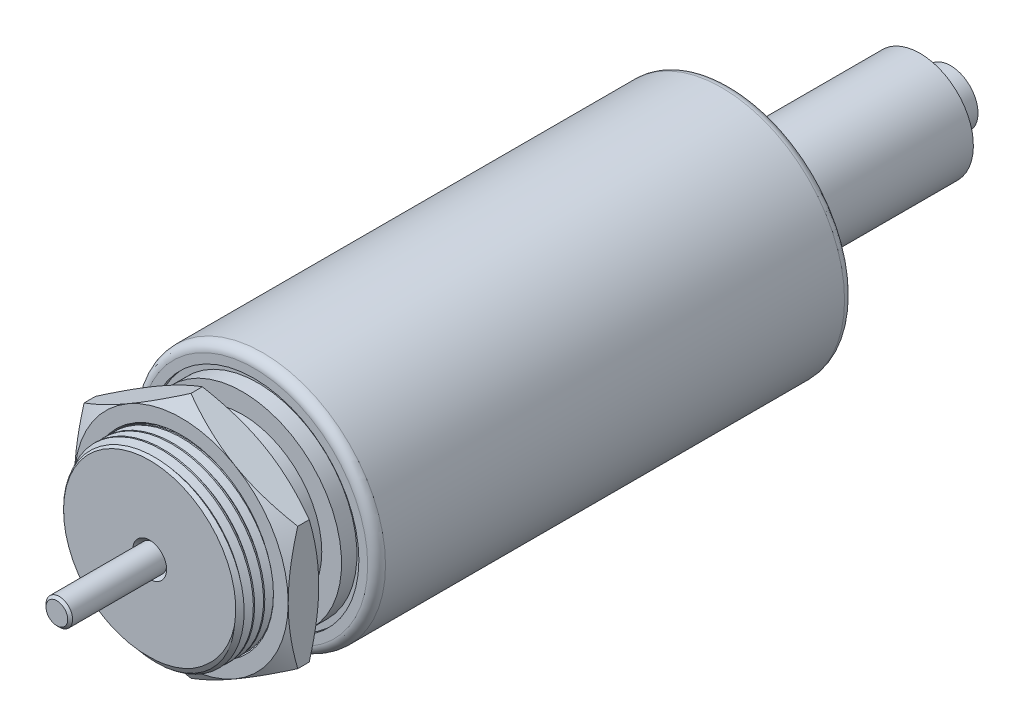
SolidWorks part; units mm, degrees
ref_plane "Front Plane" through (0, 0, 0) normal (0, 0, 1) x (1, 0, 0)
ref_plane "Top Plane" through (0, 0, 0) normal (0, 1, 0) x (1, 0, 0)
ref_plane "Right Plane" through (0, 0, 0) normal (1, 0, 0) x (0, 0, -1)
sketch "Sketch0" plane through (0, 0, 0) normal (1, 0, 0) x (0, 0, -1)
  line L0 (0, 0) -> (50.8, 0) construction
  line L1 (0, 0) -> (-19.304, 0) construction
  line L2 (50.8, 12.7635) -> (50.8, -12.7635) construction
  line L3 (0, 9.464) -> (0, -9.464) construction
  line L4 (-19.304, 1.3843) -> (-19.304, -1.3843) construction
  line L5 (-19.304, 0) -> (-32.004, 0) construction
  line L6 (50.8, 0) -> (63.5, 0) construction
  line L7 (63.5, 0) -> (73.66, 0) construction
  line L8 (70.485, 5.5499) -> (70.485, -5.5499) construction
  line L9 (73.66, 2.8575) -> (73.66, -2.8575) construction
  point P12 (-9.652, 0)
  point P17 (70.485, 0)
  dimension "D1" = 5.715
  dimension "Lg." = 50.8
  dimension "Dia." = 25.527
  dimension "Rod Dia." = 2.7686
  dimension "A" = 32.004
  dimension "Thread OD" = 18.9281
  dimension "Stroke" = 12.7
  dimension "D2" = 3.175
  dimension "D3" = 9.652
  dimension "D4" = 19.304
  dimension "End Dia." = 11.0998
  dimension "D5" = 10.16
sketch "Sketch1" plane through (0, 0, 0) normal (1, 0, 0) x (0, 0, -1)
  line L0 (50.8, 0) -> (0, 0) construction
  line L1 (49.8729, 12.7635) -> (2.1209, 12.7635)
  line L4 (1.6002, 10.922) -> (1.6002, 10.3124)
  line L5 (50.8, 5.5499) -> (50.8, 11.8364)
  line L6 (1.1938, 11.8364) -> (1.1938, 10.922)
  line L7 (1.1938, 10.922) -> (1.6002, 10.922)
  line L8 (1.6002, 10.3124) -> (0, 10.3124)
  line L9 (0, 10.3124) -> (0, 5.5499)
  line L10 (50.8, 5.5499) -> (0, 5.5499)
  line L11 (0, 9.464) -> (0, -9.464) construction
  arc A1 (50.8, 11.8364) -> (49.8729, 12.7635) centre (49.8729, 11.8364) ccw
  arc A2 (1.1938, 11.8364) -> (2.1209, 12.7635) centre (2.1209, 11.8364) cw
  dimension "D1" = 0.9271
  dimension "D4" = 1.1938
  dimension "D5" = 21.844
  dimension "D6" = 0.4064
  dimension "D7" = 20.6248
revolve "Revolve1" add sketch "Sketch1" angle 360 mid plane about L0
sketch "Sketch2" plane through (0, 0, 0) normal (1, 0, 0) x (0, 0, -1)
  line L0 (0, 0) -> (-19.304, 0) construction
  line L3 (-9.652, 1.7653) -> (-9.652, 8.956)
  line L4 (-9.652, 8.956) -> (-9.144, 9.464)
  line L5 (-9.144, 9.464) -> (-2.479, 9.464)
  line L6 (-2.479, 9.464) -> (-1.27, 8.255)
  line L7 (-1.27, 8.255) -> (0, 8.255)
  line L8 (0, 8.255) -> (0, 1.3843)
  line L9 (-9.271, 1.3843) -> (0, 1.3843)
  line L11 (-9.271, 1.3843) -> (-9.652, 1.7653)
  dimension "D1" = 1.27
  dimension "D4" = 0.508
  dimension "D5" = 9.652
  dimension "D2" = 45
  dimension "D6" = 1.209
  dimension "D3" = 45
  dimension "D8" = 0.381
  dimension "D7" = 45
revolve "Revolve2" add sketch "Sketch2" angle 360 mid plane about L0
sketch "Sketch3" plane through (0, 0, 0) normal (1, 0, 0) x (0, 0, -1)
  line L0 (-19.304, 0) -> (0, 0) construction
  line L1 (-19.05, 1.3843) -> (-19.304, 1.1303)
  line L2 (73.66, 0) -> (-19.304, 0)
  line L3 (0, 9.464) -> (0, -9.464) construction
  line L4 (12.7, 1.3843) -> (-19.05, 1.3843)
  line L5 (-19.304, 0) -> (-19.304, 1.1303)
  line L6 (-19.05, 1.3843) -> (-19.304, 1.3843) construction
  line L7 (-19.304, 1.3843) -> (-19.304, 1.1303) construction
  line L8 (0, 0) -> (0, 5.5499) construction
  line L9 (0, 5.5499) -> (12.7, 5.5499) construction
  line L10 (12.7, 5.5499) -> (70.485, 5.5499)
  line L11 (70.485, 5.5499) -> (70.485, 2.8575)
  line L12 (70.485, 2.8575) -> (73.66, 2.8575)
  line L14 (73.66, 2.8575) -> (73.66, 0)
  line L15 (-19.304, 0) -> (-32.004, 0) construction
  line L16 (12.7, 5.5499) -> (12.7, 1.3843)
  line L17 (50.8, 5.5499) -> (0, 5.5499) construction
  line L18 (73.66, 2.8575) -> (73.66, -2.8575) construction
  dimension "D1" = 0.254
revolve "Revolve3" add sketch "Sketch3" angle 360 mid plane about L2
sketch "Sketch6" plane through (0, 0, 9.652) normal (0, 0, 1) x (1, 0, 0)
  circle A1 centre (0, 0) radius 9.464
  point P1 (0, 9.464)
curve "Helix/Spiral1" pitch 1.0583 height 9.4403 radius 9.464 centre (0, 0, 9.652) axis (0, 0, -1) start towards (0, 1, 0) parameters "Pitch"=1.0583
sketch "Sketch7" plane through (0, 0, 0) normal (1, 0, 0) x (0, 0, -1)
  line L0 (-10.6442, 9.5786) -> (-9.5859, 9.5786) construction
  line L1 (-9.5859, 9.5786) -> (-10.115, 8.6621) construction
  line L2 (-10.115, 8.6621) -> (-10.6442, 9.5786) construction
  line L3 (-10.1812, 8.7766) -> (-10.0489, 8.7766) construction
  line L4 (-10.578, 9.464) -> (-9.652, 9.464) construction
  line L5 (-10.115, 8.6621) -> (-10.115, 8.7766) construction
  line L6 (-10.115, 9.464) -> (-10.115, 9.5786) construction
  line L7 (-10.1812, 8.7766) -> (-10.0489, 8.7766)
  line L8 (-10.0489, 8.7766) -> (-9.6189, 9.5213)
  line L9 (-9.6189, 9.5213) -> (-10.6111, 9.5213)
  line L10 (-10.6111, 9.5213) -> (-10.1812, 8.7766)
  line L11 (-10.115, 8.6621) -> (-10.115, -9.464) construction
  line L12 (-10.115, -9.464) -> (-9.0567, -9.464) construction
  line L13 (-9.0567, -9.464) -> (-7.9984, -9.464) construction
  line L14 (-7.9984, -9.464) -> (-6.94, -9.464) construction
  line L15 (-9.144, -9.464) -> (-2.479, -9.464) construction
  point P15 (-10.115, 9.5213)
  dimension "D1" = 1.0583
  dimension "D2" = 0.1323
sweep "Cut-Sweep1" cut profiles "Sketch7" path "Helix/Spiral1" align with end faces yes
move or copy body "Body-Move/Copy1" bodies to move or copy 105 copy yes number of copies 1 translate (0, 0, 12.7)
sketch "SketchX" plane through (0, 0, 0) normal (1, 0, 0) x (0, 0, -1)
  line L0 (57.785, 5.5499) -> (0, 5.5499) construction
  line L1 (-31.75, 1.3843) -> (-32.004, 1.1303) construction
  line L2 (57.785, -5.5499) -> (57.785, 5.5499) construction
  line L3 (-32.004, 1.1303) -> (-32.004, -1.1303) construction
  line L4 (-32.004, 1.1303) -> (-32.004, -1.1303)
  line L5 (-32.004, -1.1303) -> (-31.75, -1.3843) construction
  line L6 (-31.75, 1.3843) -> (-32.004, 1.1303)
  line L7 (60.96, 2.8575) -> (57.785, 2.8575) construction
  line L9 (-32.004, -1.1303) -> (-31.75, -1.3843)
  line L10 (60.96, -2.8575) -> (60.96, 2.8575) construction
  line L11 (57.785, -2.8575) -> (60.96, -2.8575) construction
  line L13 (0, -5.5499) -> (57.785, -5.5499) construction
  line L14 (57.785, 5.5499) -> (50.8, 5.5499)
  line L15 (57.785, -5.5499) -> (57.785, -2.8575)
  line L16 (60.96, 2.8575) -> (57.785, 2.8575)
  line L17 (60.96, -2.8575) -> (60.96, 2.8575)
  line L18 (57.785, -2.8575) -> (60.96, -2.8575)
  line L19 (50.8, -5.5499) -> (57.785, -5.5499)
  line L20 (50.8, 12.7635) -> (50.8, -12.7635) construction
  line L21 (0, 1.3843) -> (-31.75, 1.3843) construction
  line L22 (-31.75, -1.3843) -> (0, -1.3843) construction
  line L23 (-19.05, 1.3843) -> (-31.75, 1.3843)
  line L24 (-31.75, -1.3843) -> (-19.05, -1.3843)
  line L25 (57.785, 2.8575) -> (57.785, 5.5499)
delete or keep bodies "Body-Delete1" type delete bodies bodies 108
sketch "Sketch8" plane through (0, 0, -50.8) normal (0, 0, -1) x (-1, 0, 0)
  line L0 (-10.16, -2.54) -> (-10.16, 2.54) construction
  line L1 (0, 0) -> (-10.16, 0) construction
  circle A0 centre (-10.16, 2.54) radius 0.381
  circle A1 centre (-10.16, -2.54) radius 0.381
  dimension "D1" = 0.762
  dimension "D2" = 5.08
  dimension "D3" = 10.16
extrude "Boss-Extrude1" [suppressed] add sketch "Sketch8" along normal blind 152.4
sketch "Sketch9" plane through (0, 0, -50.8) normal (0, 0, -1) x (-1, 0, 0)
  circle A0 centre (-10.16, 2.54) radius 0.7874
  circle A1 centre (-10.16, -2.54) radius 0.7874
  circle A3 centre (-10.16, -2.54) radius 0.381
  circle A4 centre (-10.16, -2.54) radius 0.381
  circle A5 centre (-10.16, 2.54) radius 0.381
  circle A6 centre (-10.16, 2.54) radius 0.381
  dimension "D3" = 1.5748
  dimension "D1" = 0
  dimension "D2" = 0
extrude "Boss-Extrude2" [suppressed] add sketch "Sketch9" along normal blind 139.7
sketch "Sketch10" plane through (0, 0, 0) normal (0, 0, 1) x (1, 0, 0)
  line L0 (0, 9.464) -> (0, -9.464) construction
  line L1 (0, 9.464) -> (0, 11.1125) construction
  line L2 (0, 12.8316) -> (-11.1125, 6.4158)
  line L3 (-11.1125, 6.4158) -> (-11.1125, -6.4158)
  line L4 (-11.1125, -6.4158) -> (0, -12.8316)
  line L5 (0, -12.8316) -> (11.1125, -6.4158)
  line L6 (11.1125, -6.4158) -> (11.1125, 6.4158)
  line L7 (11.1125, 6.4158) -> (0, 12.8316)
  circle A0 centre (0, 0) radius 9.464
  circle A1 centre (0, 0) radius 11.1125 construction
  dimension "D1" = 22.225
extrude "Boss-Extrude3" add sketch "Sketch10" along normal blind 3.175 from offset 3.175 separate body
sketch "Sketch11" plane through (0, 0, 0) normal (1, 0, 0) x (0, 0, -1)
  line L0 (-6.35, 0) -> (-3.175, 0) construction
  line L1 (0, 11.1125) -> (-6.35, 11.1125) construction
  line L2 (-10.115, 9.5786) -> (-6.35, 9.5786) construction
  line L3 (-6.35, 12.8316) -> (-6.35, 11.1125)
  line L4 (-6.35, 6.4158) -> (-6.35, 12.8316) construction
  line L5 (-6.35, 11.1125) -> (-5.3575, 12.8316)
  line L6 (-6.35, 12.8316) -> (-3.175, 12.8316) construction
  line L7 (-5.3575, 12.8316) -> (-6.35, 12.8316)
  line L8 (-3.175, 12.8316) -> (-3.175, 11.1125)
  line L9 (-3.175, 6.4158) -> (-3.175, 12.8316) construction
  line L10 (-3.175, 11.1125) -> (-4.1675, 12.8316)
  line L11 (-4.1675, 12.8316) -> (-3.175, 12.8316)
  line L12 (-6.35, 9.464) -> (-6.35, -9.464) construction
  line L13 (-3.175, -9.464) -> (-3.175, 9.464) construction
  line L14 (-6.35, 9.5786) -> (-6.35, 9.464)
  line L15 (-6.35, 9.464) -> (-6.2354, 9.464)
  line L16 (-6.2354, 9.464) -> (-6.35, 9.5786)
  line L17 (-3.175, 9.5786) -> (-3.175, 9.464)
  line L18 (-3.175, 9.464) -> (-3.2896, 9.464)
  line L19 (-3.2896, 9.464) -> (-3.175, 9.5786)
  dimension "D1" = 30
revolve "Cut-Revolve1" cut sketch "Sketch11" angle 360 about L0
equation "\"D3@Helix/Spiral1\" = \"Pitch@Helix/Spiral1\" + \"D5@Sketch2\" - \"D1@Sketch2\""
equation "\"D1@Sketch7\" = \"Pitch@Helix/Spiral1\""
equation "\"D2@Sketch7\" = \"D1@Sketch7\" / 8"
